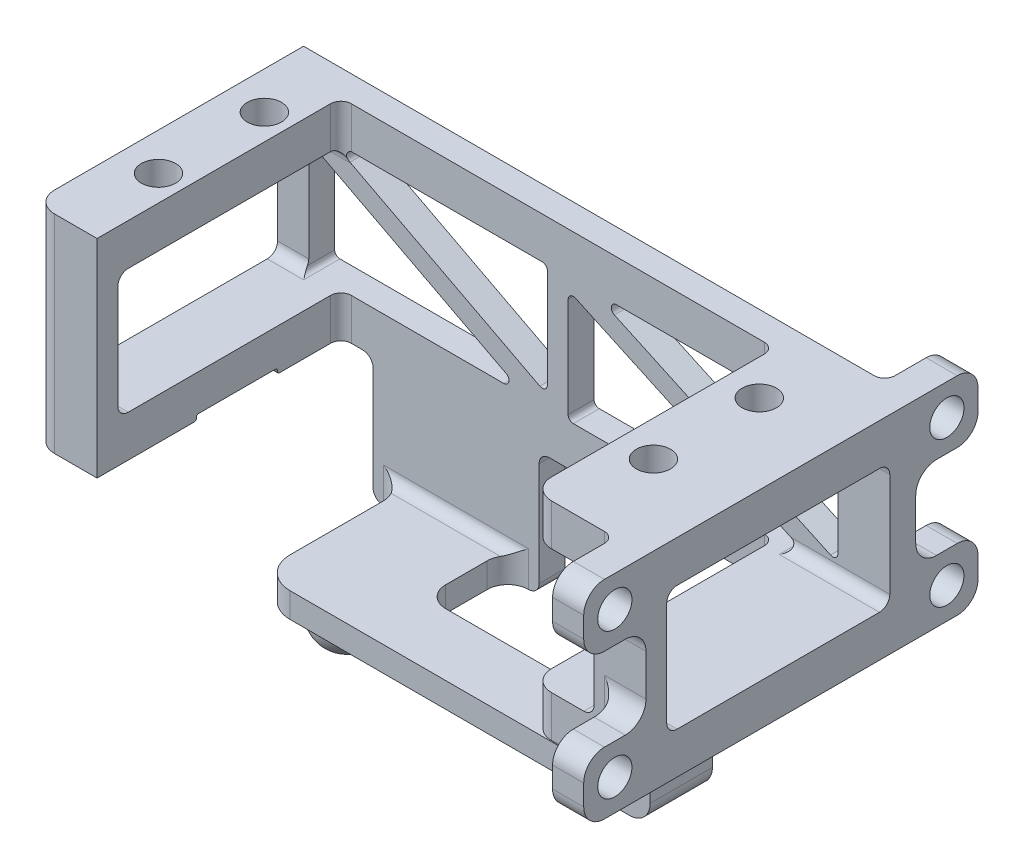
SolidWorks part; units mm, degrees
ref_plane "Plano frontal" through (0, 0, 0) normal (0, 0, 1) x (1, 0, 0)
ref_plane "Plano superior" through (0, 0, 0) normal (0, 1, 0) x (1, 0, 0)
ref_plane "Plano direito" through (0, 0, 0) normal (1, 0, 0) x (0, 0, -1)
sketch "Esboço1" plane through (0, 0, 0) normal (0, 1, 0) x (1, 0, 0)
  line L1 (-2.5, -13) -> (2.5, -13)
  line L2 (-2.5, -13) -> (-2.5, 13)
  line L3 (-2.5, 13) -> (2.5, 13)
  line L4 (2.5, -13) -> (2.5, 13)
  line L5 (-2.5, -13) -> (2.5, 13) construction
  line L6 (-2.5, 13) -> (2.5, -13) construction
  point P0 (0, 0)
  point P6 (-2.5, 0)
  dimension "D1" = 26
  dimension "D2" = 5
  dimension "D3" = 26
extrude "Ressalto-extrusão1" add sketch "Esboço1" along normal mid plane 20
sketch "Esboço2" plane through (0, 10, 0) normal (0, 1, 0) x (1, 0, 0)
  line L1 (-2.5, 13) -> (-56.5, 13)
  line L2 (-2.5, 13) -> (-2.5, -13)
  line L3 (-2.5, -13) -> (-56.5, -13)
  line L4 (-56.5, 13) -> (-56.5, -13)
  dimension "D1" = 54
extrude "Ressalto-extrusão2" add sketch "Esboço2" against normal blind 4
sketch "Esboço4" plane through (0, -10, 0) normal (0, -1, 0) x (1, 0, 0)
  line L0 (-2.5, -13) -> (-2.5, 13) construction
  line L1 (-2.5, 13) -> (-56.5, 13)
  line L2 (-2.5, 13) -> (-2.5, -13)
  line L3 (-2.5, -13) -> (-56.5, -13)
  line L4 (-56.5, 13) -> (-56.5, -13)
  line L5 (-56.5, -13) -> (-56.5, 13) construction
extrude "Ressalto-extrusão3" add sketch "Esboço4" against normal blind 4
sketch "Esboço3" plane through (0, 6, 0) normal (0, -1, 0) x (1, 0, 0)
  line L0 (-56.5, 13) -> (-2.5, 13) construction
  line L1 (-50.4, -10.5) -> (-8.6, -10.5)
  line L2 (-50.4, -10.5) -> (-50.4, 10.5)
  line L3 (-50.4, 10.5) -> (-8.6, 10.5)
  line L4 (-8.6, -10.5) -> (-8.6, 10.5)
  line L5 (-50.4, -10.5) -> (-8.6, 10.5) construction
  line L6 (-50.4, 10.5) -> (-8.6, -10.5) construction
  line L8 (-50.4, 10.5) -> (-8.6, 10.5)
  line L9 (-50.4, 10.5) -> (-50.4, 13)
  line L10 (-50.4, 13) -> (-8.6, 13)
  line L11 (-8.6, 10.5) -> (-8.6, 13)
  point P0 (-29.5, 0)
  point P7 (-29.5, 13)
  line M7 (-2.5, 13) -> (-56.5, 13)
  dimension "D1" = 41.8
  dimension "D2" = 21
extrude "Corte-extrusão1" cut sketch "Esboço3" against normal up to next and the other way up to next contours L1 L4 L3 L2 | L3 L11 L9 M7 region at (-29.5, 6, 0) region at (-29.5, 6, 11.75)
sketch "Esboço5" plane through (0, 0, -13) normal (0, 0, -1) x (-1, 0, 0)
  line L0 (2.5, 6) -> (56.5, 6) construction
  line L1 (56.5, -6) -> (53.5, -6)
  line L2 (56.5, -6) -> (56.5, 6)
  line L3 (56.5, 6) -> (53.5, 6)
  line L4 (53.5, -6) -> (53.5, 6)
  line L5 (56.5, -6) -> (2.5, -6) construction
  line L6 (28.5, -6) -> (30.5, -6)
  line L7 (28.5, -6) -> (28.5, 6)
  line L8 (28.5, 6) -> (30.5, 6)
  line L9 (30.5, -6) -> (30.5, 6)
  line L10 (30.5, -6) -> (53.5, 6)
  line L12 (30.5, -4.8721) -> (51.3381, 6)
  line L13 (32.6619, -6) -> (53.5, 4.8721)
  line L15 (2.5, -6) -> (28.5, 6)
  line L19 (2.5, -4.8986) -> (26.1137, 6)
  line L20 (2.5, 6) -> (2.5, -6) construction
  line L21 (28.5, 4.8986) -> (4.8863, -6)
  line L22 (2.5, -4.8986) -> (2.5, -6)
  line L23 (4.8863, -6) -> (2.5, -6)
  line L24 (26.1137, 6) -> (28.5, 6)
  line L25 (28.5, 4.8986) -> (28.5, 6)
  line L26 (26.1137, 6) -> (28.5, 6)
  line L27 (53.5, 6) -> (51.3381, 6)
  line L28 (32.6619, -6) -> (30.5, -6)
  point P14 (29.5, -6)
  point P15 (29.5, -6)
  line M23 (2.5, 6) -> (56.5, 6)
  dimension "D1" = 3
  dimension "D2" = 2
  dimension "D3" = 1
  dimension "D4" = 1
  dimension "D5" = 1
  dimension "D6" = 1
extrude "Ressalto-extrusão4" add sketch "Esboço5" against normal up to surface (2.5 mm away) contours L6 L9 L7 M23 | L12 L9 L10 M23 | L28 L13 L4 L10 | L4 L1 L2 M23 | L23 L21 L7 L15 | L19 L22 L15 M23 region at (-55, 0, -13) region at (-42.5316, -0.2773, -13) region at (-41.4684, 0.2773, -13) region at (-29.5, 0, -13) region at (-16.087, -0.2709, -13) region at (-14.913, 0.2709, -13) up to face at (-29.5, 8, -10.5)
sketch "Esboço6" plane through (0, 0, -13) normal (0, 0, -1) x (-1, 0, 0)
  line L0 (56.5, -10) -> (-2.5, -10) construction
  line L1 (31.3, -10) -> (47.3, -10)
  line L2 (31.3, -10) -> (31.3, -22)
  line L3 (31.3, -22) -> (47.3, -22)
  line L4 (47.3, -10) -> (47.3, -22)
  line L5 (-2.5, 10) -> (56.5, 10) construction
  line L6 (56.5, -10) -> (56.5, 10) construction
  point P8 (39.3, -10)
  dimension "D1" = 32
  dimension "D2" = 17.2
  dimension "D3" = 16
extrude "Ressalto-extrusão5" add sketch "Esboço6" against normal up to surface (2.5 mm away) up to face at (-31.5455, -0.5455, -10.5)
sketch "Esboço7" plane through (0, 0, -10.5) normal (0, 0, 1) x (1, 0, 0)
  line L0 (-31.3, -10) -> (-31.3, -22) construction
  line L1 (-47.3, -22) -> (-31.3, -22)
  line L2 (-47.3, -22) -> (-47.3, -19.6)
  line L3 (-47.3, -19.6) -> (-31.3, -19.6)
  line L4 (-31.3, -22) -> (-31.3, -19.6)
  line L5 (-8.6, 10) -> (-50.4, 10) construction
  dimension "D1" = 29.6
extrude "Ressalto-extrusão6" add sketch "Esboço7" along normal blind 14
sketch "Esboço9" plane through (0, -22, 0) normal (0, -1, 0) x (1, 0, 0)
  line L0 (-42.6429, 0) -> (0, 0) construction
sketch "Esboço8" plane through (0, -22, 0) normal (0, -1, 0) x (1, 0, 0)
  line L0 (-47.3, 3.5) -> (-31.3, 3.5) construction
  line L1 (-42.3, 0) -> (-36.3, 0)
  circle A0 centre (-39.3, 0) radius 3
  point P6 (-39.3, 3.5)
  dimension "D1" = 6
revolve "Revolução1" add sketch "Esboço8" angle 180 about L0 region at (-39.3, -22, -1.2732) reverse direction yes
sketch "Esboço10" plane through (0, -19.6, 0) normal (0, 1, 0) x (1, 0, 0)
  line L1 (-47.3, -3.5) -> (-44.3, -3.5)
  line L2 (-47.3, -3.5) -> (-47.3, 10.5)
  line L3 (-47.3, 10.5) -> (-44.3, 10.5)
  line L4 (-44.3, -3.5) -> (-44.3, 10.5)
  line L5 (-31.3, 10.5) -> (-47.3, 10.5) construction
  line L6 (-31.3, -3.5) -> (-34.3, -3.5)
  line L7 (-31.3, -3.5) -> (-31.3, 10.5)
  line L8 (-31.3, 10.5) -> (-34.3, 10.5)
  line L9 (-34.3, -3.5) -> (-34.3, 10.5)
  line L10 (-31.3, 10.5) -> (-47.3, 10.5) construction
  dimension "D1" = 3
  dimension "D2" = 3
extrude "Corte-extrusão2" cut sketch "Esboço10" against normal up to next
sketch "Sketch1" plane through (-34.3, 0, 0) normal (1, 0, 0) x (0, 0, -1)
  line L0 (-3, -22) -> (3, -22) construction
  line L1 (-3.5, -19.6) -> (2.5, -19.6)
  line L2 (-3.5, -19.6) -> (-3.5, -22)
  line L3 (-3.5, -22) -> (2.5, -22)
  line L4 (2.5, -19.6) -> (2.5, -22)
  dimension "D1" = 6
extrude "Boss-Extrude1" add sketch "Sketch1" along normal up to surface (25.7 mm away) up to face at (-8.6, -8, 1.25)
sketch "Sketch2" plane through (-8.6, 0, 0) normal (1, 0, 0) x (0, 0, -1)
  line L1 (-3.5, -19.6) -> (2.5, -19.6)
  line L2 (-3.5, -19.6) -> (-3.5, -22)
  line L3 (-3.5, -22) -> (2.5, -22)
  line L4 (2.5, -19.6) -> (2.5, -22)
extrude "Boss-Extrude2" add sketch "Sketch2" along normal blind 2
sketch "Sketch3" plane through (0, -19.6, 0) normal (0, 1, 0) x (1, 0, 0)
  line L0 (-6.6, 2.5) -> (-34.3, 2.5) construction
  line L1 (-6.6, -3.5) -> (-8.6, -3.5)
  line L2 (-6.6, -3.5) -> (-6.6, 2.5)
  line L3 (-6.6, 2.5) -> (-8.6, 2.5)
  line L4 (-8.6, -3.5) -> (-8.6, 2.5)
  line L5 (-8.6, 10.5) -> (-8.6, -13) construction
extrude "Boss-Extrude3" add sketch "Sketch3" along normal up to surface (9.6 mm away) up to face at (-51.4, -10, -3.5)
fillet "Fillet1" radius 3 3 edges at (-7.6, -10, -2.5) (-7.6, -10, 3.5) (-6.6, -10, 0.5)
fillet "Fillet4" radius 2 5 edges at (-34.3, -20.8, -2.5) (-44.3, -20.8, -10.5) (-34.3, -20.8, -10.5) (-6.6, -22, 0.5) (-8.6, -19.6, 0.5)
fillet "Fillet6" radius 3 1 edges at (-44.3, -20.8, 3.5)
fillet "Fillet7" radius 1 4 edges at (-47.3, -10, -11.75) (-31.3, -22, -11.75) (-31.3, -10, -11.75) (-47.3, -22, -11.75)
sketch "Sketch5" plane through (0, 6, 0) normal (0, -1, 0) x (1, 0, 0)
  line L0 (-50.4, -10.5) -> (-50.4, 13) construction
  line L1 (-56.5, 13) -> (-50.4, 13)
  line L2 (-56.5, 13) -> (-56.5, 11)
  line L3 (-56.5, 11) -> (-50.4, 11)
  line L4 (-50.4, 13) -> (-50.4, 11)
  dimension "D1" = 2
extrude "Boss-Extrude4" add sketch "Sketch5" along normal up to surface (12 mm away) up to face at (-48.2655, -6, -5.25)
sketch "Sketch6" plane through (0, 10, 0) normal (0, 1, 0) x (1, 0, 0)
  line L0 (-50.4, -13) -> (-50.4, 10.5) construction
  line L1 (2.5, 13) -> (-56.5, 13) construction
  circle A0 centre (-52.88, 5.6) radius 1.65
  circle A1 centre (-5.18, 5.6) radius 1.65
  dimension "D1" = 3.3
  dimension "D4" = 3.3
  dimension "D2" = 2.48
  dimension "D3" = 7.4
  dimension "D5" = 47.7
extrude "Cut-Extrude1" cut sketch "Sketch6" against normal up to next
pattern_linear "LPattern1" count 2 spacing 10.2 along (0, 0, 1) of "Cut-Extrude1"
sketch "Sketch7" plane through (0, -10, 0) normal (0, -1, 0) x (1, 0, 0)
  line L0 (-50.4, 13) -> (-56.5, 13) construction
  line L1 (-56.5, 3.4247) -> (-50.4, 3.4247)
  line L2 (-56.5, 3.4247) -> (-56.5, -4.3753)
  line L3 (-56.5, -4.3753) -> (-50.4, -4.3753)
  line L4 (-50.4, 3.4247) -> (-50.4, -4.3753)
  line L5 (-56.5, 3.4247) -> (-50.4, -4.3753) construction
  line L6 (-56.5, -4.3753) -> (-50.4, 3.4247) construction
  line L7 (-50.4, -10.5) -> (-50.4, 13) construction
  line L8 (-56.5, 13) -> (-56.5, -13) construction
  point P0 (-53.45, -0.4753)
  dimension "D1" = 13.4753
  dimension "D2" = 7.8
extrude "Cut-Extrude2" cut sketch "Sketch7" against normal blind 0.5
fillet "Fillet8" radius 0.2 4 edges at (-53.45, -10, -4.3753) (-53.45, -10, 3.4247) (-53.45, -9.5, -4.3753) (-53.45, -9.5, 3.4247)
fillet "Fillet11" radius 1 6 edges at (-50.4, -8, -10.5) (-8.6, -8, -10.5) (-50.4, 8, -10.5) (-8.6, 8, -10.5) (-2.5, 6, 0) (-2.5, -6, 1.25)
fillet "Fillet13" radius 2 1 edges at (-56.5, 0, 13)
fillet "Fillet14" radius 0.5 11 edges at (-2.5, -4.8986, -11.75) (-26.1137, 6, -11.75) (-4.8863, -6, -11.75) (-28.5, -6, -11.75) (-28.5, 4.8986, -11.75) (-30.5, -4.8721, -11.75) (-30.5, 6, -11.75) (-51.3381, 6, -11.75) (-32.6619, -6, -11.75) (-53.5, -6, -11.75) (-53.5, 4.8721, -11.75)
fillet "Fillet15" radius 1 1 edges at (-39.3, -19.6, -10.5)
sketch "Sketch8" plane through (0, 0, -13) normal (0, 0, -1) x (-1, 0, 0)
  line L0 (-2.5, 10) -> (56.5, 10) construction
  line L1 (-2.5, -10) -> (0.5, -10)
  line L2 (-2.5, -10) -> (-2.5, 10)
  line L3 (-2.5, 10) -> (0.5, 10)
  line L4 (0.5, -10) -> (0.5, 10)
  line L5 (-2.5, 10) -> (56.5, 10) construction
  line L6 (-2.5, 4) -> (0.5, 4)
  line L7 (-2.5, 4) -> (-2.5, -4)
  line L8 (-2.5, -4) -> (0.5, -4)
  line L9 (0.5, 4) -> (0.5, -4)
  line L10 (56.5, -10) -> (53.5, -10)
  line L11 (56.5, -10) -> (56.5, 10)
  line L12 (56.5, 10) -> (53.5, 10)
  line L13 (53.5, -10) -> (53.5, 10)
  line L15 (53.5, 10) -> (56.5, 10)
  line L16 (53.5, 10) -> (53.5, 4)
  line L17 (53.5, 4) -> (56.5, 4)
  line L18 (56.5, 10) -> (56.5, 4)
  line L19 (53.5, -10) -> (56.5, -10)
  line L20 (53.5, -10) -> (53.5, -4)
  line L21 (53.5, -4) -> (56.5, -4)
  line L22 (56.5, -10) -> (56.5, -4)
  line M22 (56.5, 10) -> (-2.5, 10)
  line M23 (-2.5, 10) -> (-2.5, -10)
  line M24 (-2.5, -10) -> (30.3, -10)
  dimension "D1" = 3
  dimension "D2" = 6
  dimension "D3" = 6
  dimension "D4" = 3
extrude "Boss-Extrude6" add sketch "Sketch8" along normal blind 6 contours L6 L4 M23 M22 | L8 L4 M23 M24 region at (1, -7, -13) region at (1, 7, -13)
sketch "Sketch9" plane through (2.5, 0, 0) normal (1, 0, 0) x (0, 0, -1)
  line L0 (19, -4) -> (13, -4) construction
  line L1 (19, 10) -> (19, 4) construction
  line L2 (19, -4) -> (19, -10) construction
  circle A0 centre (16, 7) radius 1.65
  circle A1 centre (16, -7) radius 1.65
  point P6 (16, -4)
  point P10 (19, 7)
  point P13 (19, -7)
  dimension "D1" = 3.3
  dimension "D2" = 3.3
extrude "Cut-Extrude3" cut sketch "Sketch9" against normal up to next
sketch "Sketch11" plane through (2.5, 0, 0) normal (1, 0, 0) x (0, 0, -1)
  line L0 (10.5, 6) -> (-11, 6) construction
  line L2 (10.5, 6) -> (10.5, -6) construction
  line L4 (10.5, 6) -> (-11, 6)
  line L5 (-11, -6) -> (-11, 6)
  line L6 (10.5, 6) -> (10.5, -6)
  line L7 (-11, -6) -> (10.5, -6)
  line L8 (-11, -6) -> (10.5, -6) construction
  line L9 (-11, -6) -> (-11, 6) construction
extrude "Cut-Extrude5" cut sketch "Sketch11" against normal up to next
mirror "Mirror1" about plane through (0, 0, 0) normal (0, 0, 1) of "Boss-Extrude6"
mirror "Mirror2" about plane through (0, 0, 0) normal (0, 0, 1) of "Cut-Extrude3"
fillet "Fillet16" radius 2 8 edges at (1, -10, 19) (1, -4, 19) (1, 4, 19) (1, 10, 19) (1, -10, -19) (1, -4, -19) (1, 4, -19) (1, 10, -19)
fillet "Fillet17" radius 2 4 edges at (1, -4, 13) (1, 4, 13) (1, -4, -13) (1, 4, -13)
fillet "Fillet18" radius 1 8 edges at (-54.75, -6, -10.5) (-53.45, -6, 11) (-52.95, 6, -10.5) (-53.45, 6, 11) (-0.5, 6, -10.5) (-0.5, 6, 11) (-0.5, -6, 11) (-2.3314, -6, -10.5)
fillet "Fillet19" radius 1 4 edges at (-0.5, -6, -13) (-0.5, 6, -13) (-0.5, 6, 13) (-0.5, -6, 13)
fillet "Fillet20" radius 2 2 edges at (-8.6, 8, 13) (-8.6, -8, 13)
equation "\"Folga_total\"= 1mm'Folga devido ao encaixe"
equation "\"D1@Esboço3\"=\"Folga_total\"+40.8"
equation "\"D2@Esboço3\"=\"Folga_total\"+20"
equation "\"D1@Esboço10\"=\"D2@Esboço10\""
equation "\"D4@Sketch6\"=\"D1@Sketch6\""
equation "\"D2@Sketch9\"=\"D1@Sketch9\""
equation "\"D4@Sketch8\"=\"D1@Sketch8\""
